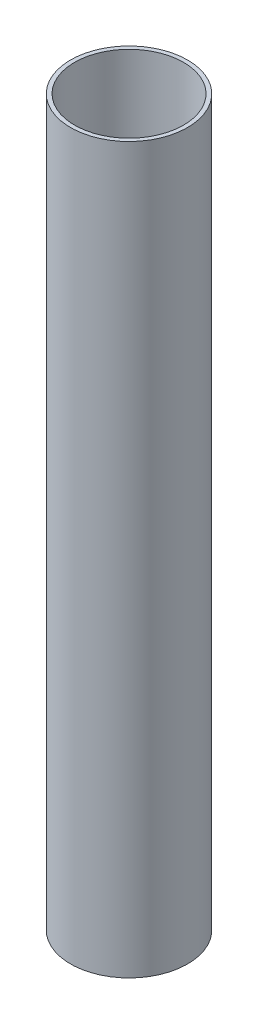
SolidWorks part; units mm, degrees
ref_plane "Front Plane" through (0, 0, 0) normal (0, 0, 1) x (1, 0, 0)
ref_plane "Top Plane" through (0, 0, 0) normal (0, 1, 0) x (1, 0, 0)
ref_plane "Right Plane" through (0, 0, 0) normal (1, 0, 0) x (0, 0, -1)
sketch "Sketch1" plane through (0, 0, 0) normal (0, 0, 1) x (1, 0, 0)
  line L0 (0, 0) -> (0, 304.8) construction
  line L1 (-20.5232, 0) -> (-19.1008, 0)
  line L2 (-20.5232, 0) -> (-20.5232, 254)
  line L3 (-20.5232, 254) -> (-19.1008, 254)
  line L4 (20.5232, 0) -> (20.5232, 254)
  line L5 (-19.1008, 0) -> (-19.1008, 254)
  line L6 (19.1008, 254) -> (19.1008, 0)
  line L7 (19.1008, 0) -> (20.5232, 0)
  line L8 (19.1008, 254) -> (20.5232, 254)
  dimension "D1" = 41.0464
  dimension "12" = 254
  dimension "D2" = 38.2016
revolve "Revolve2" add sketch "Sketch1" angle 360 about L0 region at (-19.812, 127, 0)
